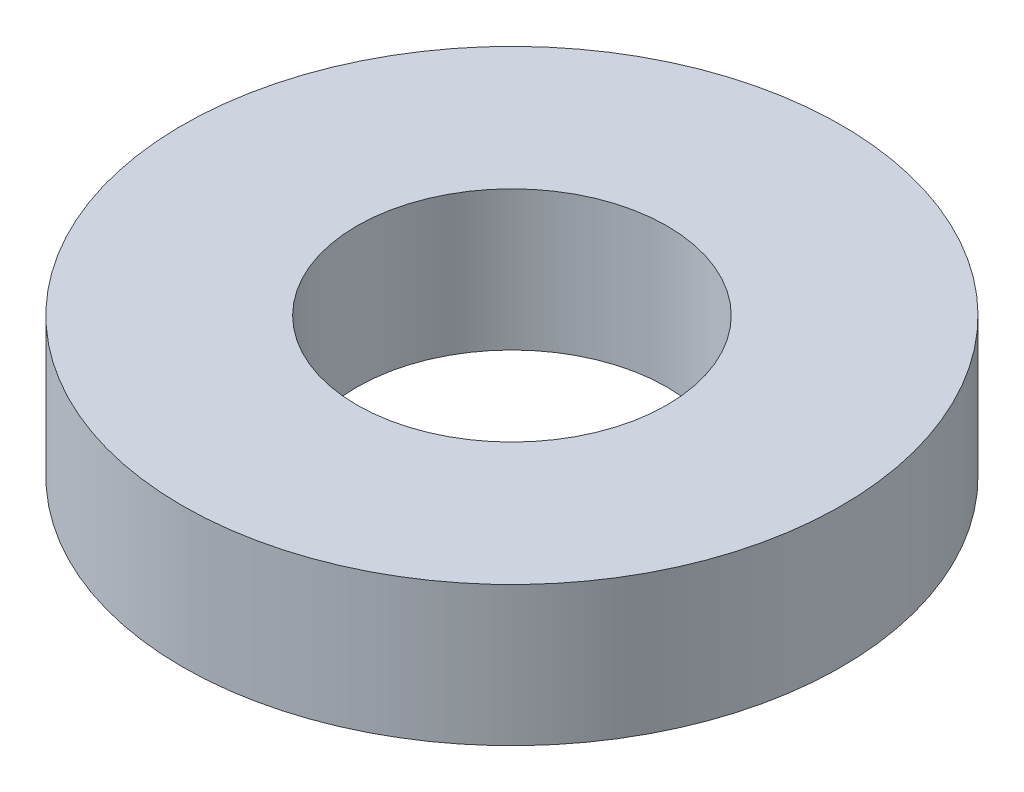
SolidWorks part; units mm, degrees
ref_plane "Front Plane" through (0, 0, 0) normal (0, 0, 1) x (1, 0, 0)
ref_plane "Top Plane" through (0, 0, 0) normal (0, 1, 0) x (1, 0, 0)
ref_plane "Right Plane" through (0, 0, 0) normal (1, 0, 0) x (0, 0, -1)
sketch "Sketch1" plane through (0, 0, 0) normal (0, 1, 0) x (1, 0, 0)
  circle A0 centre (0, 0) radius 42.5
  dimension "FLANGE_OD" = 85
extrude "Boss-Extrude1" add sketch "Sketch1" along normal blind 18
sketch "Sketch2" plane through (0, 0, 0) normal (0, 1, 0) x (1, 0, 0)
  circle A0 centre (0, 0) radius 20
  dimension "BORE_D" = 40
extrude "Cut-Extrude1" cut sketch "Sketch2" along normal through all
sketch "Sketch3" plane through (0, 18, 0) normal (0, 1, 0) x (1, 0, 0)
  circle A0 centre (0, 0) radius 13.5764 construction
  circle A1 centre (-13.5764, 0) radius 3.6361
  dimension "BOLT_D" = 7.2723
  dimension "BOLT_PCD" = 27.1528
extrude "Cut-Extrude2" cut sketch "Sketch3" against normal blind 13.7066 rebuild error yes
pattern_circular "CirPattern1" count 5 over 360 rebuild error yes
